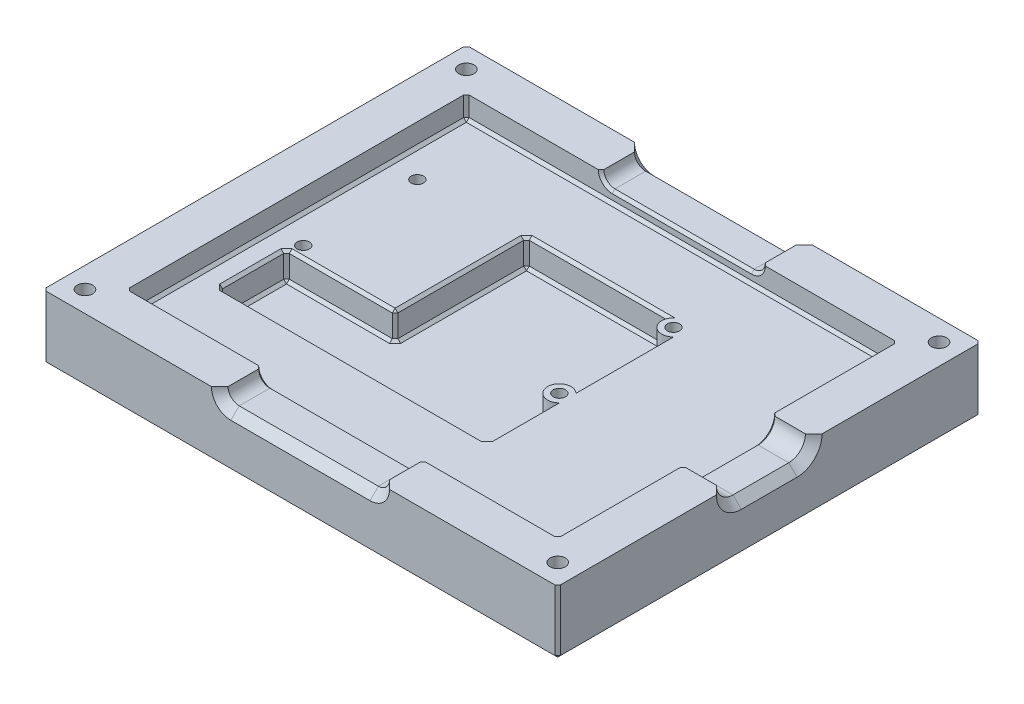
SolidWorks part; units mm, degrees
note: The reader was unsure of these and kept them because the rebuilt part matched: shared geometry of "Sketch2<2>".
ref_plane "Front Plane" through (0, 0, 0) normal (0, 0, 1) x (1, 0, 0)
ref_plane "Top Plane" through (0, 0, 0) normal (0, 1, 0) x (1, 0, 0)
ref_plane "Right Plane" through (0, 0, 0) normal (1, 0, 0) x (0, 0, -1)
sketch "Sketch1" plane through (0, 0, 0) normal (0, 1, 0) x (1, 0, 0)
  line L0 (8, 49.3997) -> (8, 25.4)
  line L1 (0, 0) -> (154.8, 0)
  line L2 (0, 0) -> (0, 121.9997)
  line L3 (0, 121.9997) -> (154.8, 121.9997)
  line L4 (154.8, 0) -> (154.8, 121.9997)
  line L5 (8, 25.4) -> (104, 25.4)
  line L6 (104, 25.4) -> (104, 49.7065)
  line L7 (104, 57.0929) -> (104, 90.7065)
  line L8 (98.4223, 96.5997) -> (47, 96.5997)
  line L9 (47, 96.5997) -> (47, 49.3997)
  line L10 (47, 49.3997) -> (8, 49.3997)
  circle A0 centre (10, 53.3997) radius 2.2
  circle A1 centre (10, 94.3997) radius 2.2
  circle A2 centre (102, 94.3997) radius 2.2
  circle A3 centre (102, 53.3997) radius 2.2
  arc A4 (104, 49.7065) -> (104, 57.0929) centre (102, 53.3997) cw
  arc A5 (104, 90.7065) -> (98.4223, 96.5997) centre (102, 94.3997) cw
  dimension "D2" = 4.4
  dimension "D7" = 2
  dimension "D8" = 2
  dimension "D1" = 92
  dimension "D3" = 41
  dimension "D4" = 37
  dimension "D5" = 2
  dimension "D6" = 27.9997
  dimension "D9" = 2
  dimension "D10" = 50.8
  dimension "D11" = 25.4
  dimension "D12" = 25.4
  dimension "D13" = 8
  dimension "D14" = 4
extrude "Boss-Extrude1" add sketch "Sketch1" along normal blind 10
sketch "Sketch2" plane through (0, 0, 0) normal (0, -1, 0) x (1, 0, 0)
  line L0 (154.8, 0) -> (154.8, -121.9997) construction
  line L1 (0, 0) -> (154.8, 0)
  line L2 (0, 0) -> (0, -121.9997)
  line L3 (0, -121.9997) -> (154.8, -121.9997)
  line L4 (154.8, 0) -> (154.8, -121.9997)
  line L5 (154.8, -121.9997) -> (0, -121.9997) construction
  line L6 (-15, 15) -> (-15, -136.9997)
  line L7 (-15, -136.9997) -> (169.8, -136.9997)
  line L8 (169.8, 15) -> (169.8, -136.9997)
  line L9 (-15, 15) -> (169.8, 15)
  line M11 (0, 0) -> (0, -121.9997)
  line M12 (0, -121.9997) -> (154.8, -121.9997)
  line M13 (154.8, -121.9997) -> (154.8, 0)
  line M14 (154.8, 0) -> (0, 0)
  dimension "D1" = 15
extrude "Boss-Extrude2" add sketch "Sketch2" against normal blind 18
extrude "Boss-Extrude3" add sketch "Sketch2<2>" along normal blind 5 contours L9 L6 L7 L8 M11 M14 M13 M12 | L2 L1 L4 L3
sketch "Sketch2<2>" plane through (0, 0, 0) normal (0, -1, 0) x (1, 0, 0) same geometry as "Sketch2"
sketch "Sketch3" plane through (0, 0, 15) normal (0, 0, 1) x (1, 0, 0)
  line L0 (52.4, 18) -> (102.4, 18) construction
  line L1 (169.8, 18) -> (-15, 18) construction
  line L2 (52.4, 22) -> (102.4, 22)
  line L3 (52.4, 14) -> (102.4, 14)
  arc A0 (52.4, 22) -> (52.4, 14) centre (52.4, 18) ccw
  arc A1 (102.4, 14) -> (102.4, 22) centre (102.4, 18) ccw
  point P4 (77.4, 18)
  point P9 (77.4, 18)
  dimension "D1" = 8
  dimension "D2" = 50
extrude "Cut-Extrude1" cut sketch "Sketch3" against normal through all
sketch "Sketch4" plane through (169.8, 0, 0) normal (1, 0, 0) x (0, 0, -1)
  line L0 (50.9998, 18) -> (70.9998, 18) construction
  line L1 (136.9997, 18) -> (-15, 18) construction
  line L2 (50.9998, 24) -> (70.9998, 24)
  line L3 (50.9998, 12) -> (70.9998, 12)
  arc A0 (50.9998, 24) -> (50.9998, 12) centre (50.9998, 18) ccw
  arc A1 (70.9998, 12) -> (70.9998, 24) centre (70.9998, 18) ccw
  point P4 (60.9998, 18)
  point P9 (60.9998, 18)
  dimension "D1" = 12
  dimension "D2" = 20
extrude "Cut-Extrude2" cut sketch "Sketch4" against normal up to next
sketch "Sketch5" plane through (0, 18, 0) normal (0, 1, 0) x (1, 0, 0)
  line L0 (-15, 136.9997) -> (0, 121.9997) construction
  line L1 (154.8, 0) -> (169.8, -15) construction
  line L2 (0, 0) -> (154.8, 0) construction
  line L3 (154.8, 0) -> (106.4, 0) construction
  point P11 (162.3, -7.5)
  point P12 (-7.5, 129.4997)
  point P14 (-7.5, -7.5)
  point P15 (162.3, 129.4997)
hole_wizard "M5 Clearance Hole1" positions "Sketch5" profile "Sketch6" hole size "M5" standard "ANSI Metric"
sketch "Sketch6" plane through (162.3, 18, -129.4997) normal (1, 0, 0) x (0, 0, 1)
  line L0 (0, 0) -> (0, 24.6524)
  line L1 (0, 24.6524) -> (2.75, 23)
  line L2 (2.75, 23) -> (2.75, 0)
  line L5 (2.75, 0) -> (0, 0)
  line L10 (0, 24.6524) -> (-2.75, 23) construction
  line L11 (0, -6.35) -> (0, 107.95) construction
  dimension "Hole Dia." = 5.5
  dimension "Hole Depth" = 23
  dimension "Drill Angle" = 118
sketch "Sketch7" plane through (0, -5, 0) normal (0, -1, 0) x (1, 0, 0)
  line L1 (-3.4, 9.8671) -> (-7.5, 12.2343)
  line L2 (-7.5, 12.2343) -> (-11.6, 9.8671)
  line L3 (-11.6, 9.8671) -> (-11.6, 5.1329)
  line L4 (-11.6, 5.1329) -> (-7.5, 2.7657)
  line L5 (-7.5, 2.7657) -> (-3.4, 5.1329)
  line L6 (-3.4, 5.1329) -> (-3.4, 9.8671)
  line L7 (158.2, 9.8671) -> (158.2, 5.1329)
  line L8 (158.2, 5.1329) -> (162.3, 2.7657)
  line L9 (162.3, 2.7657) -> (166.4, 5.1329)
  line L10 (166.4, 5.1329) -> (166.4, 9.8671)
  line L11 (166.4, 9.8671) -> (162.3, 12.2343)
  line L12 (162.3, 12.2343) -> (158.2, 9.8671)
  line L13 (158.2, -127.1326) -> (158.2, -131.8668)
  line L14 (158.2, -131.8668) -> (162.3, -134.234)
  line L15 (162.3, -134.234) -> (166.4, -131.8668)
  line L16 (166.4, -131.8668) -> (166.4, -127.1326)
  line L17 (166.4, -127.1326) -> (162.3, -124.7654)
  line L18 (162.3, -124.7654) -> (158.2, -127.1326)
  line L19 (-3.4, -127.1326) -> (-7.5, -124.7654)
  line L20 (-7.5, -124.7654) -> (-11.6, -127.1326)
  line L21 (-11.6, -127.1326) -> (-11.6, -131.8668)
  line L22 (-11.6, -131.8668) -> (-7.5, -134.234)
  line L23 (-7.5, -134.234) -> (-3.4, -131.8668)
  line L24 (-3.4, -131.8668) -> (-3.4, -127.1326)
  circle A0 centre (-7.5, 7.5) radius 4.1 construction
  circle A1 centre (162.3, 7.5) radius 4.1 construction
  circle A2 centre (162.3, -129.4997) radius 4.1 construction
  circle A3 centre (-7.5, -129.4997) radius 4.1 construction
  dimension "D1" = 8.2
extrude "Cut-Extrude3" cut sketch "Sketch7" against normal blind 6
chamfer "Chamfer1" distance 1 angle 45 46 edges at (0, 10, -60.9998) (0, 14, 0) (77.4, 10, 0) (49.5716, 15.1716, 0) (77.4, 14, 0) (105.2284, 15.1716, 0) (154.8, 13.7574, -46.7572) (154.8, 14, 0) (154.8, 10, -60.9998) (154.8, 12, -60.9998) (154.8, 13.7574, -75.2425) (105.2284, 15.1716, -121.9997) (154.8, 14, -121.9997) (77.4, 10, -121.9997) (0, 14, -121.9997) (49.5716, 15.1716, -121.9997) (77.4, 14, -121.9997) (104, 10, -37.5532) (8, 10, -37.3999) (104, 5, -25.4) (56, 10, -25.4) (8, 5, -25.4) (98.9496, 0, -91.5126) (104, 0, -73.8997) (97.8, 0, -53.3997) (104, 0, -37.5532) (56, 0, -25.4) (8, 0, -37.3999) (27.5, 0, -49.3997) (47, 0, -72.9997) (72.7111, 0, -96.5997) (104, 10, -73.8997) (72.7111, 10, -96.5997) (27.5, 10, -49.3997) (47, 10, -72.9997) (169.8, 6.5, -136.9997) (169.8, 6.5, 15) (-15, 6.5, 15) (-15, 6.5, -136.9997) (-15, -5, -60.9998) (77.4, -5, -136.9997) (169.8, -5, -60.9998) (77.4, -5, 15) (47, 5, -96.5997) (47, 5, -49.3997) (8, 5, -49.3997)
chamfer "Chamfer2" distance 3 angle 45 9 edges at (49.5716, 15.1716, 15) (105.2284, 15.1716, 15) (77.4, 14, 15) (169.8, 13.7574, -46.7572) (169.8, 13.7574, -75.2425) (169.8, 12, -60.9998) (49.5716, 15.1716, -136.9997) (105.2284, 15.1716, -136.9997) (77.4, 14, -136.9997)
